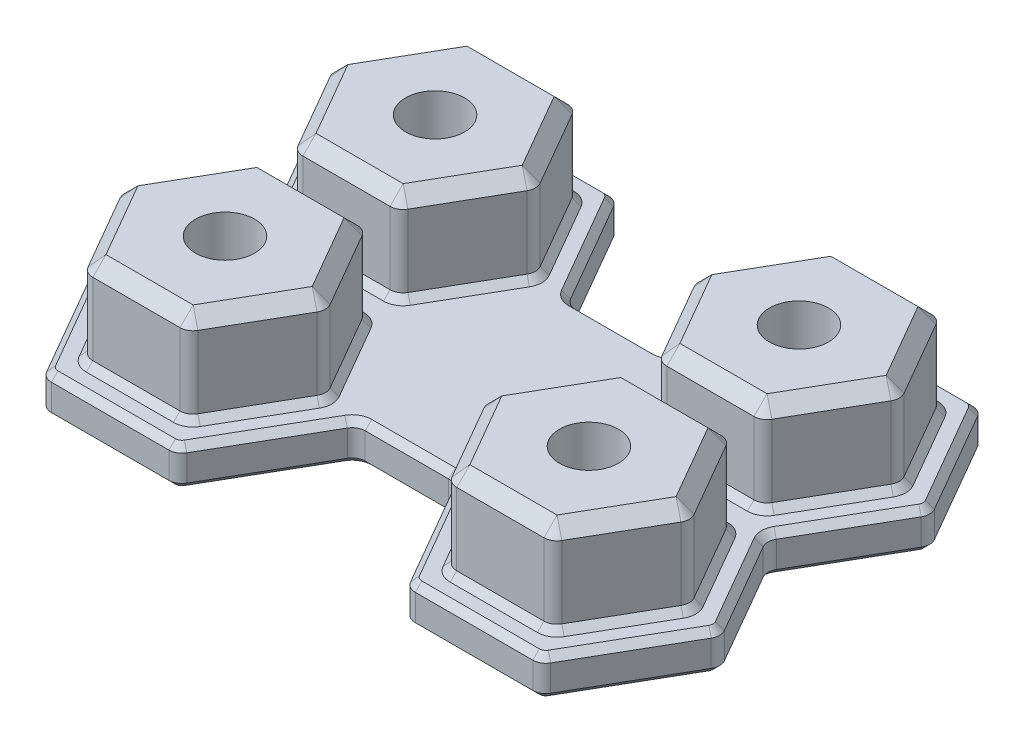
SolidWorks part; units mm, degrees
note: The reader was unsure of these and kept them because the rebuilt part matched: shared geometry of "Sketch1<3>".
ref_plane "Front Plane" through (0, 0, 0) normal (0, 0, 1) x (1, 0, 0)
ref_plane "Top Plane" through (0, 0, 0) normal (0, 1, 0) x (1, 0, 0)
ref_plane "Right Plane" through (0, 0, 0) normal (1, 0, 0) x (0, 0, -1)
sketch "Sketch1" plane through (0, 0, 0) normal (0, 1, 0) x (1, 0, 0)
  line L0 (35.5142, -16) -> (31.6171, -9.25) construction
  line L1 (4.1858, -6.25) -> (7.5056, -0.5)
  line L2 (7.5056, 0.5) -> (4.1858, 6.25)
  line L3 (3.3198, 6.75) -> (-3.3198, 6.75)
  line L4 (-4.1858, 6.25) -> (-7.5056, 0.5)
  line L5 (-7.5056, -0.5) -> (-4.1858, -6.25)
  line L6 (-3.3198, -6.75) -> (3.3198, -6.75)
  line L7 (31.9058, -6.25) -> (35.2256, -0.5)
  line L8 (35.2256, 0.5) -> (31.9058, 6.25)
  line L9 (31.0398, 6.75) -> (24.4002, 6.75)
  line L10 (23.5342, 6.25) -> (20.2144, 0.5)
  line L11 (20.2144, -0.5) -> (23.5342, -6.25)
  line L12 (24.4002, -6.75) -> (31.0398, -6.75)
  line L13 (4.1858, -22.25) -> (7.5056, -16.5)
  line L14 (7.5056, -15.5) -> (4.1858, -9.75)
  line L15 (3.3198, -9.25) -> (-3.3198, -9.25)
  line L16 (-4.1858, -9.75) -> (-7.5056, -15.5)
  line L17 (-7.5056, -16.5) -> (-4.1858, -22.25)
  line L18 (-3.3198, -22.75) -> (3.3198, -22.75)
  line L19 (31.9058, -22.25) -> (35.2256, -16.5)
  line L20 (35.2256, -15.5) -> (31.9058, -9.75)
  line L21 (31.0398, -9.25) -> (24.4002, -9.25)
  line L22 (23.5342, -9.75) -> (20.2144, -15.5)
  line L23 (20.2144, -16.5) -> (23.5342, -22.25)
  line L24 (24.4002, -22.75) -> (31.0398, -22.75)
  line L25 (9.815, 0.5) -> (5.3405, 8.25)
  line L26 (4.4745, 8.75) -> (-4.4745, 8.75)
  line L27 (-5.3405, 8.25) -> (-9.815, 0.5)
  line L28 (-9.815, -0.5) -> (-5.7735, -7.5)
  line L29 (-5.7735, -8.5) -> (-9.815, -15.5)
  line L30 (-9.815, -16.5) -> (-5.3405, -24.25)
  line L31 (-4.4745, -24.75) -> (4.4745, -24.75)
  line L32 (5.3405, -24.25) -> (9.815, -16.5)
  line L33 (31.6171, -22.75) -> (35.5142, -16) construction
  line L34 (23.8229, -22.75) -> (31.6171, -22.75) construction
  line L35 (17.905, -16.5) -> (22.3795, -24.25)
  line L36 (23.2455, -24.75) -> (32.1945, -24.75)
  line L37 (33.0605, -24.25) -> (37.535, -16.5)
  line L38 (37.535, -15.5) -> (33.4935, -8.5)
  line L39 (33.4935, -7.5) -> (37.535, -0.5)
  line L40 (37.535, 0.5) -> (33.0605, 8.25)
  line L41 (32.1945, 8.75) -> (23.2455, 8.75)
  line L42 (22.3795, 8.25) -> (17.905, 0.5)
  line L43 (19.9258, -16) -> (23.8229, -22.75) construction
  line L44 (-5.6292, -8.25) -> (-10.1036, -16) construction
  line L45 (-10.1036, 0) -> (-5.6292, -7.75) construction
  line L46 (10.681, -16) -> (17.039, -16)
  line L47 (10.681, 0) -> (17.039, 0)
  line L48 (33.3492, -7.75) -> (37.8236, 0) construction
  line L49 (37.8236, -16) -> (33.3492, -8.25) construction
  line L50 (5.6292, -7.75) -> (10.1036, 0) construction
  line L51 (10.1036, -16) -> (5.6292, -8.25) construction
  line L52 (22.0908, -8.25) -> (17.6164, -16) construction
  line L53 (17.6164, 0) -> (22.0908, -7.75) construction
  line L54 (23.8229, -9.25) -> (19.9258, -16) construction
  line L55 (31.6171, 6.75) -> (23.8229, 6.75) construction
  line L56 (23.8229, 6.75) -> (19.9258, 0) construction
  line L57 (35.5142, 0) -> (31.6171, 6.75) construction
  line L58 (31.6171, -6.75) -> (35.5142, 0) construction
  line L59 (19.9258, 0) -> (23.8229, -6.75) construction
  line L60 (7.7942, -16) -> (3.8971, -9.25) construction
  line L61 (3.8971, -22.75) -> (7.7942, -16) construction
  line L62 (-3.8971, -22.75) -> (3.8971, -22.75) construction
  line L63 (-7.7942, -16) -> (-3.8971, -22.75) construction
  line L64 (-3.8971, -9.25) -> (-7.7942, -16) construction
  line L65 (-3.8971, 6.75) -> (-7.7942, 0) construction
  line L66 (-7.7942, 0) -> (-3.8971, -6.75) construction
  line L67 (3.8971, -6.75) -> (7.7942, 0) construction
  line L68 (7.7942, 0) -> (3.8971, 6.75) construction
  line L69 (3.8971, 6.75) -> (-3.8971, 6.75) construction
  line L70 (10.1036, 0) -> (5.0518, 8.75) construction
  line L71 (5.0518, 8.75) -> (-5.0518, 8.75) construction
  line L72 (22.6682, 8.75) -> (17.6164, 0) construction
  line L73 (32.7718, 8.75) -> (22.6682, 8.75) construction
  line L74 (37.8236, 0) -> (32.7718, 8.75) construction
  line L75 (32.7718, -24.75) -> (37.8236, -16) construction
  line L76 (22.6682, -24.75) -> (32.7718, -24.75) construction
  line L77 (17.6164, -16) -> (22.6682, -24.75) construction
  line L78 (5.0518, -24.75) -> (10.1036, -16) construction
  line L79 (-5.0518, -24.75) -> (5.0518, -24.75) construction
  line L80 (-10.1036, -16) -> (-5.0518, -24.75) construction
  line L81 (-5.0518, 8.75) -> (-10.1036, 0) construction
  circle A0 centre (0, 0) radius 6.75 construction
  circle A1 centre (27.72, 0) radius 6.75 construction
  circle A2 centre (0, -16) radius 6.75 construction
  circle A3 centre (27.72, -16) radius 6.75 construction
  arc A4 (31.9058, -9.75) -> (31.0398, -9.25) centre (31.0398, -10.25) ccw
  arc A5 (35.2256, -16.5) -> (35.2256, -15.5) centre (34.3595, -16) ccw
  arc A6 (31.9058, -22.25) -> (31.0398, -22.75) centre (31.0398, -21.75) cw
  arc A7 (23.5342, -22.25) -> (24.4002, -22.75) centre (24.4002, -21.75) ccw
  arc A8 (20.2144, -15.5) -> (20.2144, -16.5) centre (21.0805, -16) ccw
  arc A9 (24.4002, -9.25) -> (23.5342, -9.75) centre (24.4002, -10.25) ccw
  arc A10 (24.4002, 6.75) -> (23.5342, 6.25) centre (24.4002, 5.75) ccw
  arc A11 (31.9058, 6.25) -> (31.0398, 6.75) centre (31.0398, 5.75) ccw
  arc A12 (35.2256, -0.5) -> (35.2256, 0.5) centre (34.3595, 0) ccw
  arc A13 (31.9058, -6.25) -> (31.0398, -6.75) centre (31.0398, -5.75) cw
  arc A14 (23.5342, -6.25) -> (24.4002, -6.75) centre (24.4002, -5.75) ccw
  arc A15 (20.2144, 0.5) -> (20.2144, -0.5) centre (21.0805, 0) ccw
  arc A16 (4.1858, -9.75) -> (3.3198, -9.25) centre (3.3198, -10.25) ccw
  arc A17 (7.5056, -16.5) -> (7.5056, -15.5) centre (6.6395, -16) ccw
  arc A18 (4.1858, -22.25) -> (3.3198, -22.75) centre (3.3198, -21.75) cw
  arc A19 (-4.1858, -22.25) -> (-3.3198, -22.75) centre (-3.3198, -21.75) ccw
  arc A20 (-7.5056, -15.5) -> (-7.5056, -16.5) centre (-6.6395, -16) ccw
  arc A21 (-3.3198, -9.25) -> (-4.1858, -9.75) centre (-3.3198, -10.25) ccw
  arc A22 (-7.5056, 0.5) -> (-7.5056, -0.5) centre (-6.6395, 0) ccw
  arc A23 (-4.1858, -6.25) -> (-3.3198, -6.75) centre (-3.3198, -5.75) ccw
  arc A24 (4.1858, -6.25) -> (3.3198, -6.75) centre (3.3198, -5.75) cw
  arc A25 (7.5056, -0.5) -> (7.5056, 0.5) centre (6.6395, 0) ccw
  arc A26 (4.1858, 6.25) -> (3.3198, 6.75) centre (3.3198, 5.75) ccw
  arc A27 (-3.3198, 6.75) -> (-4.1858, 6.25) centre (-3.3198, 5.75) ccw
  arc A28 (5.3405, 8.25) -> (4.4745, 8.75) centre (4.4745, 7.75) ccw
  arc A29 (17.905, 0.5) -> (17.039, 0) centre (17.039, 1) cw
  arc A30 (10.681, 0) -> (9.815, 0.5) centre (10.681, 1) cw
  arc A31 (23.2455, 8.75) -> (22.3795, 8.25) centre (23.2455, 7.75) ccw
  arc A32 (33.0605, 8.25) -> (32.1945, 8.75) centre (32.1945, 7.75) ccw
  arc A33 (37.535, -0.5) -> (37.535, 0.5) centre (36.6689, 0) ccw
  arc A34 (33.4935, -8.5) -> (33.4935, -7.5) centre (34.3595, -8) cw
  arc A35 (37.535, -16.5) -> (37.535, -15.5) centre (36.6689, -16) ccw
  arc A36 (32.1945, -24.75) -> (33.0605, -24.25) centre (32.1945, -23.75) ccw
  arc A37 (22.3795, -24.25) -> (23.2455, -24.75) centre (23.2455, -23.75) ccw
  arc A38 (17.039, -16) -> (17.905, -16.5) centre (17.039, -17) cw
  arc A39 (9.815, -16.5) -> (10.681, -16) centre (10.681, -17) cw
  arc A40 (4.4745, -24.75) -> (5.3405, -24.25) centre (4.4745, -23.75) ccw
  arc A41 (-5.3405, -24.25) -> (-4.4745, -24.75) centre (-4.4745, -23.75) ccw
  arc A42 (-9.815, -15.5) -> (-9.815, -16.5) centre (-8.9489, -16) ccw
  arc A43 (-5.7735, -8.5) -> (-5.7735, -7.5) centre (-6.6395, -8) ccw
  arc A44 (-9.815, -0.5) -> (-9.815, 0.5) centre (-8.9489, 0) cw
  arc A45 (-4.4745, 8.75) -> (-5.3405, 8.25) centre (-4.4745, 7.75) ccw
  dimension "D5" = 1
  dimension "D1" = 27.72
  dimension "D2" = 13.5
  dimension "D3" = 16
  dimension "D4" = 2
extrude "Boss-Extrude1" add sketch "Sketch1" along normal blind 3 contours L15 A21 L16 A20 L17 A19 L18 A18 L13 A17 L14 A16 | L3 A27 L4 A22 L5 A23 L6 A24 L1 A25 L2 A26 | L10 A15 L11 A14 L12 A13 L7 A12 L8 A11 L9 A10 | L21 A9 L22 A8 L23 A7 L24 A6 L19 A5 L20 A4 | L26 A45 L27 A44 L28 A43 L29 A42 L30 A41 L31 A40 L32 A39 L46 A38 L35 A37 L36 A36 L37 A35 L38 A34 L39 A33 L40 A32 L41 A31 L42 A29 L47 A30 L25 A28 A9 L21 A4 L20 A5 L19 A6 L24 A7 L23 A8 L22 A15
extrude "Boss-Extrude2" add sketch "Sketch1<3>" along normal blind 7 from surface at 3 contours L3 A27 L4 A22 L5 A23 L6 A24 L1 A25 L2 A26 | L10 A15 L11 A14 L12 A13 L7 A12 L8 A11 L9 A10 | L21 A9 L22 A8 L23 A7 L24 A6 L19 A5 L20 A4 | L15 A21 L16 A20 L17 A19 L18 A18 L13 A17 L14 A16 starting at face at (13.86, 3, 8)
sketch "Sketch1<3>" plane through (0, 0, 0) normal (0, 1, 0) x (1, 0, 0) same geometry as "Sketch1"
chamfer "Chamfer1" distance 1 angle 45 48 edges at (27.72, 10, -6.75) (31.5398, 10, -6.616) (33.5657, 10, -3.375) (35.3595, 10, 0) (33.5657, 10, 3.375) (31.5398, 10, 6.616) (27.72, 10, 6.75) (23.9002, 10, 6.616) (21.8743, 10, 3.375) (20.0805, 10, 0) (21.8743, 10, -3.375) (23.9002, 10, -6.616) (33.5657, 10, 12.625) (35.3595, 10, 16) (33.5657, 10, 19.375) (31.5398, 10, 22.616) (27.72, 10, 22.75) (23.9002, 10, 22.616) (21.8743, 10, 19.375) (20.0805, 10, 16) (21.8743, 10, 12.625) (23.9002, 10, 9.384) (27.72, 10, 9.25) (31.5398, 10, 9.384) (5.8457, 10, -3.375) (7.6395, 10, 0) (5.8457, 10, 3.375) (3.8198, 10, 6.616) (0, 10, 6.75) (-3.8198, 10, 6.616) (-5.8457, 10, 3.375) (-7.6395, 10, 0) (-5.8457, 10, -3.375) (-3.8198, 10, -6.616) (0, 10, -6.75) (3.8198, 10, -6.616) (5.8457, 10, 12.625) (7.6395, 10, 16) (5.8457, 10, 19.375) (3.8198, 10, 22.616) (0, 10, 22.75) (-3.8198, 10, 22.616) (-5.8457, 10, 19.375) (-7.6395, 10, 16) (-5.8457, 10, 12.625) (-3.8198, 10, 9.384) (0, 10, 9.25) (3.8198, 10, 9.384)
chamfer "Chamfer3" distance 0.5 angle 45 120 edges at (0, 0, 24.75) (4.9745, 0, 24.616) (-4.9745, 0, 24.616) (7.5777, 0, 20.375) (-7.5777, 0, 20.375) (10.181, 0, 16.134) (-9.9489, 0, 16) (13.86, 0, 16) (-7.7942, 0, 12) (17.539, 0, 16.134) (-5.6395, 0, 8) (20.1423, 0, 20.375) (-7.7942, 0, 4) (22.7455, 0, 24.616) (-9.9489, 0, 0) (27.72, 0, 24.75) (-7.5777, 0, -4.375) (32.6945, 0, 24.616) (-4.9745, 0, -8.616) (35.2977, 0, 20.375) (0, 0, -8.75) (37.6689, 0, 16) (4.9745, 0, -8.616) (35.5142, 0, 12) (7.5777, 0, -4.375) (33.3595, 0, 8) (10.181, 0, -0.134) (35.5142, 0, 4) (13.86, 0, 0) (37.6689, 0, 0) (17.539, 0, -0.134) (35.2977, 0, -4.375) (20.1423, 0, -4.375) (32.6945, 0, -8.616) (22.7455, 0, -8.616) (27.72, 0, -8.75) (13.86, 3, 16) (10.181, 3, 16.134) (17.539, 3, 16.134) (7.5777, 3, 20.375) (20.1423, 3, 20.375) (4.9745, 3, 24.616) (22.7455, 3, 24.616) (0, 3, 24.75) (27.72, 3, 24.75) (-4.9745, 3, 24.616) (32.6945, 3, 24.616) (-7.5777, 3, 20.375) (35.2977, 3, 20.375) (-9.9489, 3, 16) (37.6689, 3, 16) (-7.7942, 3, 12) (35.5142, 3, 12) (-5.6395, 3, 8) (33.3595, 3, 8) (-7.7942, 3, 4) (35.5142, 3, 4) (-9.9489, 3, 0) (37.6689, 3, 0) (-7.5777, 3, -4.375) (35.2977, 3, -4.375) (-4.9745, 3, -8.616) (32.6945, 3, -8.616) (0, 3, -8.75) (27.72, 3, -8.75) (4.9745, 3, -8.616) (22.7455, 3, -8.616) (7.5777, 3, -4.375) (20.1423, 3, -4.375) (10.181, 3, -0.134) (17.539, 3, -0.134) (13.86, 3, 0) (33.5657, 3, 19.375) (31.5398, 3, 22.616) (35.3595, 3, 16) (27.72, 3, 22.75) (33.5657, 3, 12.625) (23.9002, 3, 22.616) (31.5398, 3, 9.384) (21.8743, 3, 19.375) (27.72, 3, 9.25) (20.0805, 3, 16) (23.9002, 3, 9.384) (21.8743, 3, 12.625) (5.8457, 3, 19.375) (3.8198, 3, 22.616) (7.6395, 3, 16) (0, 3, 22.75) (5.8457, 3, 12.625) (-3.8198, 3, 22.616) (3.8198, 3, 9.384) (-5.8457, 3, 19.375) (0, 3, 9.25) (-7.6395, 3, 16) (-3.8198, 3, 9.384) (-5.8457, 3, 12.625) (0, 3, 6.75) (-3.8198, 3, 6.616) (3.8198, 3, 6.616) (-5.8457, 3, 3.375) (5.8457, 3, 3.375) (-7.6395, 3, 0) (7.6395, 3, 0) (-5.8457, 3, -3.375) (5.8457, 3, -3.375) (-3.8198, 3, -6.616) (3.8198, 3, -6.616) (0, 3, -6.75) (27.72, 3, 6.75) (23.9002, 3, 6.616) (31.5398, 3, 6.616) (21.8743, 3, 3.375) (33.5657, 3, 3.375) (20.0805, 3, 0) (35.3595, 3, 0) (21.8743, 3, -3.375) (33.5657, 3, -3.375) (23.9002, 3, -6.616) (31.5398, 3, -6.616) (27.72, 3, -6.75)
sketch "Sketch2" plane through (0, 0, 0) normal (0, -1, 0) x (1, 0, 0)
  point P0 (0, 16)
  point P1 (0, 0)
  point P3 (27.72, 0)
  point P5 (27.72, 16)
hole_wizard "CBORE for M4 Pan Head Screw1" positions "Sketch2" profile "Sketch3" counterbore size "M4" standard "ISO" end condition through all
sketch "Sketch3" plane through (0, 0, 16) normal (1, 0, 0) x (0, 0, -1)
  line L0 (0, 0) -> (0, 10)
  line L1 (0, 10) -> (2.25, 10)
  line L3 (2.25, 10) -> (2.25, 3.1)
  line L4 (2.25, 3.1) -> (4.5, 3.1)
  line L5 (4.5, 3.1) -> (4.5, 0)
  line L7 (4.5, 0) -> (0, 0)
  line L11 (0, -6.35) -> (0, 107.95) construction
  dimension "Thru Hole Dia." = 4.5
  dimension "Thru Hole Depth" = 10
  dimension "C'Bore Dia." = 9
  dimension "C'Bore Depth" = 3.1
